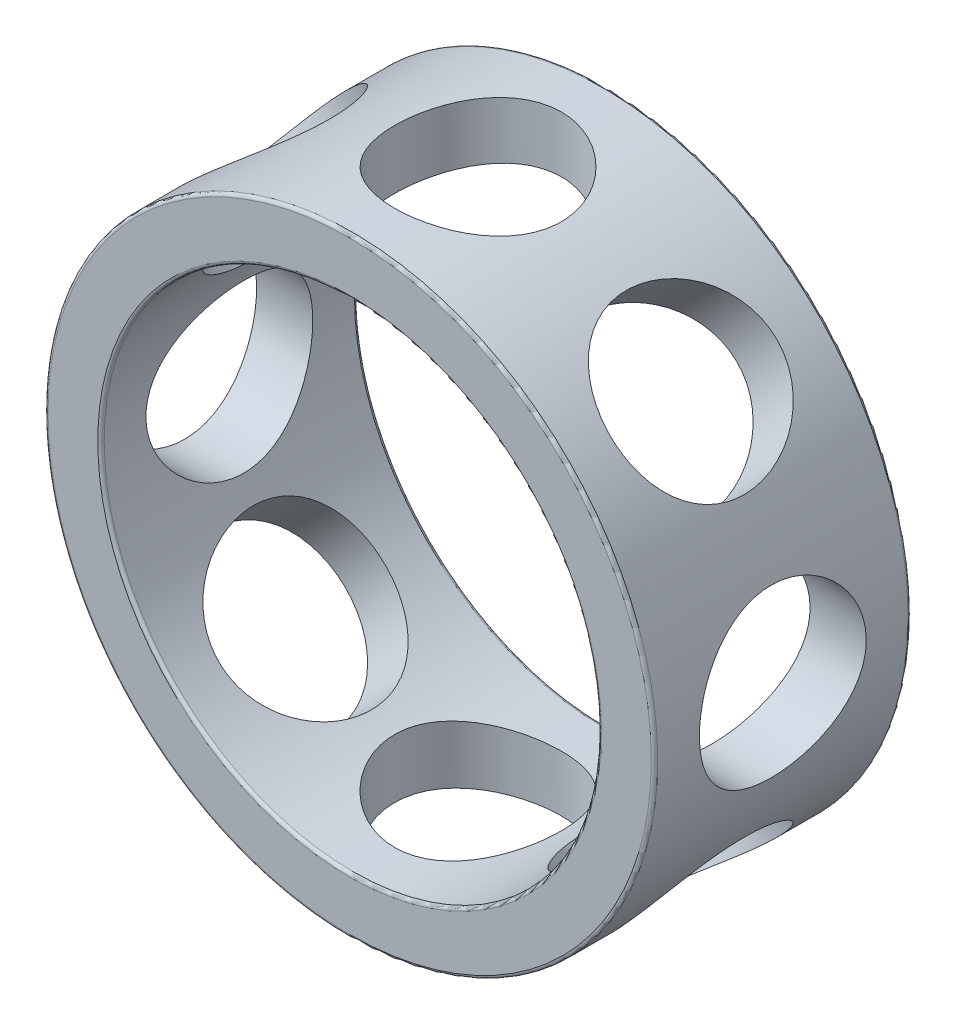
SolidWorks part; units mm, degrees
material "POM Ацеталь кополимер"
ref_plane "Спереди  XY" through (0, 0, 0) normal (0, 0, 1) x (1, 0, 0)
ref_plane "Сверху  XZ" through (0, 0, 0) normal (0, 1, 0) x (1, 0, 0)
ref_plane "Справа  ZY" through (0, 0, 0) normal (1, 0, 0) x (0, 0, -1)
sketch "Эскиз1" plane through (0, 0, 0) normal (0, 0, 1) x (1, 0, 0)
  circle A0 centre (0, 0) radius 7.75
  circle A1 centre (0, 0) radius 9.5
  dimension "D1" = 19
  dimension "D2" = 15.5
extrude "Бобышка-Вытянуть1" add sketch "Эскиз1" along normal blind 4 and the other way blind 4
sketch "Эскиз2" plane through (0, 0, 0) normal (0, 1, 0) x (1, 0, 0)
  circle A0 centre (0, 0) radius 2.6
  dimension "D1" = 5.2
extrude "Вырез-Вытянуть1" cut sketch "Эскиз2" along normal up to next
pattern_circular "Круговой массив1" count 8 over 360 about axis through (0, 0, 4) along (0, 0, 1) of "Вырез-Вытянуть1"
fillet "Скругление1" radius 0.1 4 edges at (7.75, 0, -4) (9.5, 0, -4) (7.75, 0, 4) (9.5, 0, 4)
